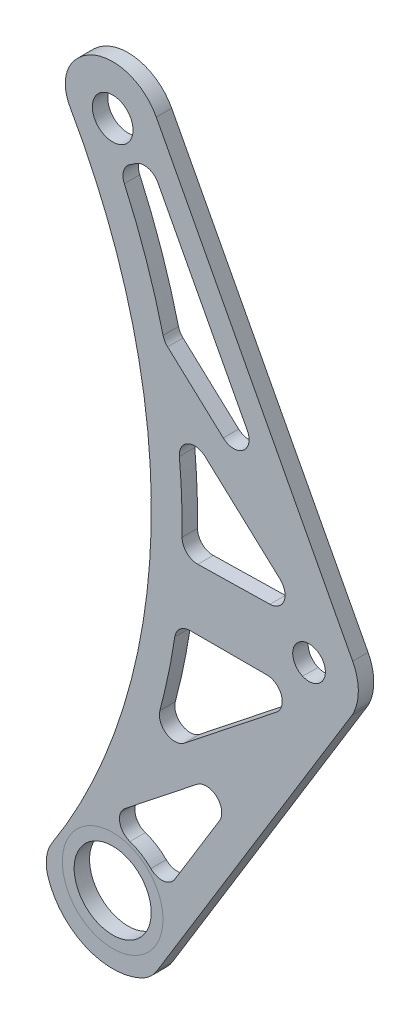
SolidWorks part; units mm, degrees
material "6061-T6 (SS)"
ref_plane "X-Y Datum" through (0, 0, 0) normal (0, 0, 1) x (1, 0, 0)
ref_plane "X-Z Datum" through (0, 0, 0) normal (0, 1, 0) x (1, 0, 0)
ref_plane "Y-Z Datum" through (0, 0, 0) normal (1, 0, 0) x (0, 0, -1)
sketch "Sketch1" plane through (0, 0, 0) normal (0, 0, 1) x (1, 0, 0)
  line L0 (0, 0) -> (0, 137.7747) construction
  line L1 (0, 137.7747) -> (40.4627, 60.9059) construction
  line L2 (40.4627, 60.9059) -> (0, 0) construction
  line L3 (-13.97, 0) -> (-10.16, 137.7747)
  line L4 (8.9905, 142.5072) -> (49.4532, 65.6383)
  line L5 (49.4532, 56.1734) -> (8.1778, -11.3263)
  circle A0 centre (0, 0) radius 7.9375
  circle A1 centre (40.4627, 60.9059) radius 3.3655
  circle A2 centre (0, 137.7747) radius 4.191
  arc A3 (-10.16, 137.7747) -> (8.9905, 142.5072) centre (0, 137.7747) cw
  arc A4 (49.4532, 65.6383) -> (49.4532, 56.1734) centre (40.4627, 60.9059) cw
  arc A5 (8.1778, -11.3263) -> (-13.97, 0) centre (0, 0) cw
  arc A6 (-10.16, 137.7747) -> (-13.97, 0) centre (-120.7988, 71.8942) cw
  circle A7 centre (0, 0) radius 11.5718
  point P16 (50.6227, 60.9059)
  dimension "D4" = 15.875
  dimension "D5" = 6.731
  dimension "D6" = 8.382
  dimension "D7" = 13.97
  dimension "D8" = 10.16
  dimension "D9" = 10.16
  dimension "D1" = 137.7747
  dimension "D2" = 86.868
  dimension "D3" = 73.1215
  dimension "D11" = 125.83
extrude "Boss-Extrude1" add sketch "Sketch1" along normal blind 3.175 contours A3 A6 A5 L5 A4 L4 A2 A1 A0 | A6 A7 A0 region at (18.3481, 68.0312, 0) region at (-11.2445, 0, 0)
sketch "Sketch2" plane through (0, 0, 3.175) normal (0, 0, 1) x (1, 0, 0)
  line L0 (10.2643, 4.258) -> (40.9141, 54.3809)
  line L1 (49.4532, 56.1734) -> (8.1778, -11.3263) construction
  line L2 (43.0391, 66.9176) -> (6.9798, 135.4209)
  line L3 (8.9905, 142.5072) -> (49.4532, 65.6383) construction
  line L4 (40.3324, 67.4451) -> (14.2277, 66.9247)
  line L5 (40.4627, 54.3654) -> (13.1773, 54.3654)
  line L6 (40.3324, 67.4451) -> (12.6913, 92.8047)
  line L7 (36.2571, 79.8016) -> (10.6112, 103.3307)
  line L8 (40.9141, 54.3809) -> (6.7632, 27.3433)
  line L9 (31.3137, 38.6811) -> (1.9613, 15.4424)
  arc A4 (0.9614, 130.4717) -> (-0.1243, 11.1118) centre (-120.7988, 71.8942) cw
  arc A5 (-13.97, 0) -> (-10.16, 137.7747) centre (-120.7988, 71.8942) ccw construction
  circle A7 centre (0, 0) radius 11.1125
  circle A9 centre (40.4627, 60.9059) radius 6.5405
  circle A10 centre (0, 137.7747) radius 7.366
  circle A11 centre (0, 137.7747) radius 4.191 construction
  circle A12 centre (40.4627, 60.9059) radius 3.3655 construction
  circle A13 centre (0, 0) radius 7.9375 construction
  dimension "D3" = 3.175
  dimension "D1" = 3.175
  dimension "D2" = 3.175
  dimension "D6" = 6.35
  dimension "D4" = 5.08
  dimension "D5" = 6.35
  dimension "D7" = 6.35
  dimension "D8" = 6.35
extrude "Cut-Extrude1" cut sketch "Sketch2" against normal blind 6.35 contours A7 L0 L9 A4 | A9 L5 A4 L8 | L6 A4 L4 | A10 A4 L7 L2 region at (13.9132, 19.1225, 3.175) region at (20.6464, 45.5257, 3.175) region at (22.7038, 75.5881, 3.175) region at (15.7766, 109.4189, 3.175)
fillet "Fillet1" radius 3.175 14 edges at (1.9613, 15.4424, 1.5875) (-0.1243, 11.1118, 1.5875) (10.2643, 4.258, 1.5875) (31.3137, 38.6811, 1.5875) (40.9141, 54.3809, 1.5875) (6.7632, 27.3433, 1.5875) (13.1773, 54.3654, 1.5875) (12.6913, 92.8047, 1.5875) (14.2277, 66.9247, 1.5875) (40.3324, 67.4451, 1.5875) (36.2571, 79.8016, 1.5875) (10.6112, 103.3307, 1.5875) (0.9614, 130.4717, 1.5875) (6.9798, 135.4209, 1.5875)
sketch "Sketch3" [suppressed] plane through (0, 0, 4.7625) normal (0, 0, 1) x (1, 0, 0)
  line L1 (13.9694, 0.1347) -> (39.7508, 21.6818)
  line L2 (9.979, 66.6708) -> (39.902, 40.8139)
  line L3 (55.423, 60.7241) -> (9.3949, 172.5239) construction
  line L6 (12.9992, 5.1168) -> (35.8725, 24.2335)
  line L8 (8.1778, -11.3263) -> (55.423, 52.9883) construction
  arc A0 (39.902, 40.8139) -> (35.8725, 24.2335) centre (43.2483, 31.2208) ccw
  arc A1 (-1.655, 13.8716) -> (12.9992, 5.1168) centre (0, 0) cw
  arc A3 (0.9228, 58.462) -> (-1.655, 13.8716) centre (-31.1833, 37.9483) cw
  circle A4 centre (43.2483, 31.2208) radius 10.16
  circle A5 centre (0, 0) radius 13.97
  arc A6 (0.9228, 58.462) -> (9.979, 66.6708) centre (0, 68.58) ccw
  circle A7 centre (0, 68.58) radius 10.16
  arc A8 (-5.9452, 60.3411) -> (-7.4548, 11.8147) centre (-23.0858, 36.5876) cw
  arc A9 (-13.4408, 9.525) -> (-10.5128, 62.23) centre (-35.7711, 37.1994) ccw construction
  dimension "D1" = 10.16
  dimension "D2" = 10.16
  dimension "D3" = 13.97
  dimension "D6" = 6.7275
  dimension "D9" = 12.7
  dimension "D7" = 38.1
  dimension "D4" = 29.81
  dimension "D5" = 5.08
  dimension "D8" = 5.08
  dimension "D11" = 75.318
extrude "Cut-Extrude2" [suppressed] cut sketch "Sketch3" against normal blind 6.35 contours A6 A3 A1 L6 A0 L2 | A5 L1 A4 L6 | L6 A0 L2 A6 A3 A1
sketch3d "3DSketch1"
  line L0 (0, 137.7747, 3.175) -> (0, 137.7747, 0) construction
  line L1 (40.4627, 60.9059, 3.175) -> (40.4627, 60.9059, 0) construction
  point P0 (0, 137.7747, 3.175)
  point P1 (40.4627, 60.9059, 3.175)
fillet "Fillet2" [suppressed] radius 6.35
fillet "Fillet4" [suppressed] radius 6.35
ref_axis "Axis1" through (0, 137.7747, 3.175) along (0, 0, -1)
ref_axis "Axis2" through (40.4627, 60.9059, 3.175) along (0, 0, -1)
ref_plane "Plane1" through (23.5609, 4.1544, 0) normal (0.9848, 0.1736, 0) x (0, 0, -1)
ref_plane "Plane2" through (11.7449, -5.1092, 0) normal (0.917, -0.3989, 0) x (0, 0, -1)
sketch "Sketch4" [suppressed] plane through (23.5609, 4.1544, 0) normal (0.9848, 0.1736, 0) x (0, 0, -1)
  line L0 (-3.175, 166.0937) -> (-3.175, 170.2847)
sketch "Sketch5" plane through (11.7449, -5.1092, 0) normal (0.917, -0.3989, 0) x (0, 0, -1)
  line L0 (-3.175, 71.991) -> (-3.175, 11.4039)
  line L1 (-0.3461, 48.6622) -> (-0.3461, 36.6839)
split line "Split Line1" [suppressed]
split line "Split Line2" [suppressed]
ref_point "Point2" [suppressed]
ref_axis "Axis3" through (0, 0, 3.175) along (0, 0, -1)
sketch "Sketch6" plane through (0, 0, 3.175) normal (0, 0, -1) x (-1, 0, 0)
  circle A0 centre (0, 0) radius 10.3708
split line "Split Line3"
fillet "Fillet5" radius 7.62 4 edges at (-13.97, 0, 1.5875) (-10.16, 137.7747, 1.5875) (49.4532, 56.1734, 1.5875) (8.1778, -11.3263, 1.5875)
ref_point "Point4" [suppressed]
ref_plane "Plane3" through (11.7921, -5.1298, 0.2245) normal (0.9169, -0.3988, 0.0175) x (-0.3989, -0.917, 0)
split line "Split Line4"
ref_point "Point6"
sketch "Sketch7" plane through (11.7921, -5.1298, 0.2245) normal (0.9169, -0.3988, 0.0175) x (-0.3989, -0.917, 0)
  line L0 (-71.991, -2.951) -> (-57.7118, -2.951)
  line L1 (-71.991, -2.951) -> (-71.991, 6.3339)
ref_point "Point8"
